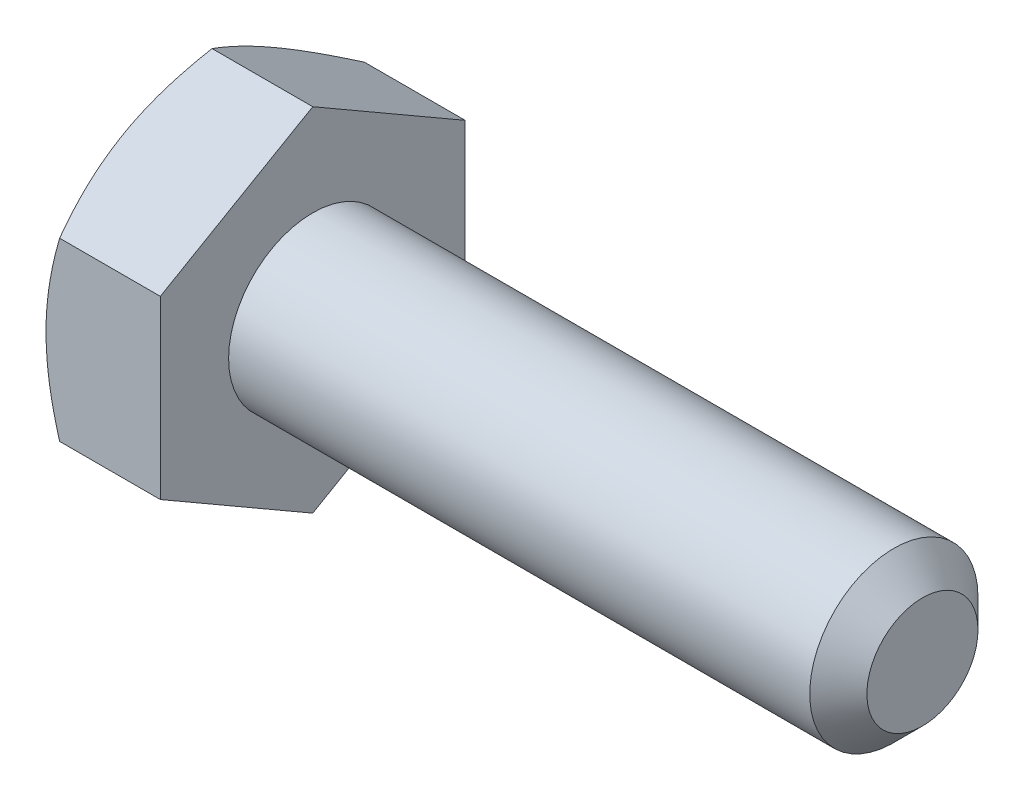
SolidWorks part; units mm, degrees
material "Alloy Steel"
ref_plane "Front Plane" through (0, 0, 0) normal (0, 0, 1) x (1, 0, 0)
ref_plane "Top Plane" through (0, 0, 0) normal (0, 1, 0) x (1, 0, 0)
ref_plane "Right Plane" through (0, 0, 0) normal (1, 0, 0) x (0, 0, -1)
sketch "Sketch1" plane through (0, 0, 0) normal (0, 0, 1) x (1, 0, 0)
  line L0 (-7.5406, 0) -> (7.5406, 0) construction
  line L1 (7.5406, 1.7526) -> (7.5406, -1.7526) construction
  line L2 (-5.1594, 3.175) -> (-5.1594, -3.175) construction
  line L3 (-7.5406, 3.175) -> (-7.5406, -3.175) construction
  point P9 (-5.1594, 0)
  point P10 (4.7625, -1.7526)
  dimension "Screw Dia" = 3.5052
  dimension "Hex" = 6.35
  dimension "Head Ht" = 2.3813
  dimension "Screw Lenght" = 12.7
  dimension "D1" = 2.7781
ref_plane "Plane2" through (7.5406, 0, 0) normal (1, 0, 0) x (0, 0, -1)
sketch "Sketch5" plane through (7.5406, 0, 0) normal (1, 0, 0) x (0, 0, -1)
  circle A0 centre (0, 0) radius 1.7526
extrude "Boss-Extrude3" add sketch "Sketch5" against normal up to vertex (12.7 mm away) up to point (-5.1594, 0, 0)
sketch "Sketch9" plane through (7.5406, 0, 0) normal (1, 0, 0) x (0, 0, -1)
  circle A1 centre (0, 0) radius 1.7526
  circle A2 centre (0, 0) radius 1.7526
  dimension "D1" = 0
curve "Helix/Spiral1" pitch 0.7937 height 13.4937 turns 17 parameters "Pitch"=0.7937
chamfer "Chamfer1" distance 0.5953 angle 45 1 edges at (7.5406, 0, -1.7526)
sketch "Sketch10" plane through (0, 0, 0) normal (0, 0, 1) x (1, 0, 0)
  line L0 (7.5406, 1.7526) -> (7.8383, 1.237)
  line L1 (7.8383, 1.237) -> (7.9375, 1.237)
  line L2 (7.9375, 1.237) -> (8.2352, 1.7526)
  line L3 (7.5406, 1.7526) -> (8.2352, 1.7526)
  line L4 (7.8879, 1.7526) -> (7.8879, 1.237) construction
  line L5 (7.6895, 1.4948) -> (8.0863, 1.4948) construction
  dimension "D1" = 60
  dimension "D2" = 0.0992
  dimension "D3" = 0.3969
sweep "Cut-Sweep1" [suppressed] cut profiles "Sketch10" path "Helix/Spiral1"
sketch "Sketch6" plane through (-5.1594, 0, 0) normal (-1, 0, 0) x (0, 0, 1)
  line L0 (0, 3.175) -> (0, -3.175) construction
  line L1 (3.175, 1.8331) -> (0, 3.6662)
  line L2 (0, 3.6662) -> (-3.175, 1.8331)
  line L3 (-3.175, 1.8331) -> (-3.175, -1.8331)
  line L4 (-3.175, -1.8331) -> (0, -3.6662)
  line L5 (0, -3.6662) -> (3.175, -1.8331)
  line L6 (3.175, -1.8331) -> (3.175, 1.8331)
  circle A0 centre (0, 0) radius 3.175 construction
extrude "Boss-Extrude4" add sketch "Sketch6" along normal up to vertex (2.3813 mm away) up to point (-7.5406, -3.175, 0)
sketch "Sketch7" plane through (-7.5406, 0, 0) normal (-1, 0, 0) x (0, 0, 1)
  circle A0 centre (0, 0) radius 3.175 construction
  circle A1 centre (0, 0) radius 3.175
sketch "Sketch8" plane through (-7.5406, 0, 0) normal (-1, 0, 0) x (0, 0, 1)
  circle A0 centre (0, 0) radius 3.175 construction
  circle A1 centre (0, 0) radius 3.175
extrude "Cut-Extrude3" cut sketch "Sketch8" against normal through all draft 60 flip side to cut
sketch "Sketch12" plane through (-7.5406, 0, 0) normal (-1, 0, 0) x (0, 0, 1)
  line L0 (0, 2.4448) -> (0, 1.3653) construction
  line L1 (0.0953, 2.4448) -> (0.0953, 1.3653)
  line L2 (-0.0952, 2.4448) -> (-0.0952, 1.3653)
  line L3 (0, 1.7526) -> (0, -1.7526) construction
  arc A0 (0.0953, 2.4448) -> (-0.0952, 2.4448) centre (0, 2.4448) ccw
  arc A1 (-0.0952, 1.3653) -> (0.0953, 1.3653) centre (0, 1.3653) ccw
  circle A3 centre (0, 0) radius 1.27 construction
  circle A4 centre (0, 0) radius 2.54 construction
  point P2 (0, 1.905)
  dimension "D1" = 2.54
  dimension "D3" = 5.08
  dimension "D2" = 0.1905
extrude "Cut-Extrude4" cut sketch "Sketch12" against normal blind 0.254
pattern_circular "CirPattern1" count 6 over 360 about axis through (-5.1594, 0, 0) along (1, 0, 0) of "Cut-Extrude4"
equation "\"D2@Sketch10\" = \"Pitch@Helix/Spiral1\"*.125"
equation "\"D3@Sketch10\" = \"Pitch@Helix/Spiral1\"*.5"
equation "\"D3@Helix/Spiral1\" = \"Screw Lenght@Sketch1\"+\"Pitch@Helix/Spiral1\""
equation "\"D1@Chamfer1\" = \"Pitch@Helix/Spiral1\"*.75"
equation "\"D1@Sketch12\" = \"Hex@Sketch1\"*.4"
equation "\"D3@Sketch12\" = \"Hex@Sketch1\"*.8"
equation "\"D2@Sketch12\" = \"Hex@Sketch1\"*.03"
equation "\"D1@Sketch1\" = \"Pitch@Helix/Spiral1\"*3.5"
